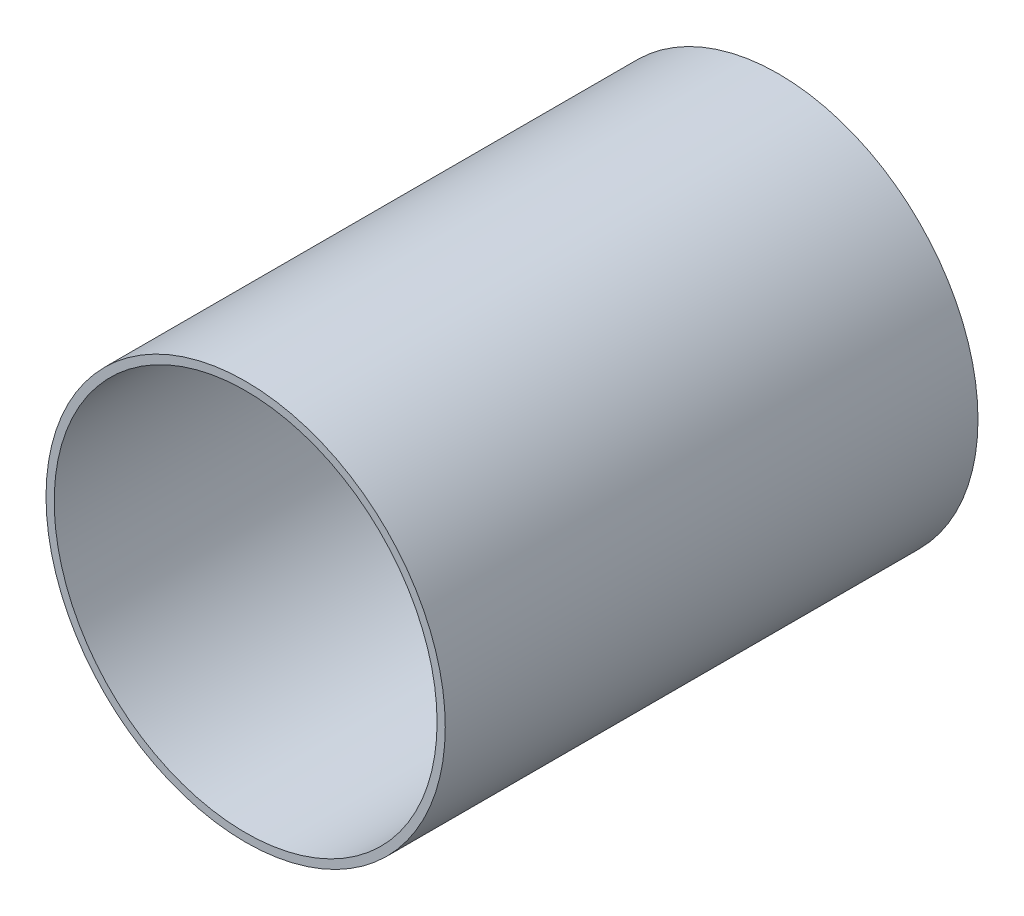
SolidWorks part; units mm, degrees
ref_plane "Front Plane" through (0, 0, 0) normal (0, 0, 1) x (1, 0, 0)
ref_plane "Top Plane" through (0, 0, 0) normal (0, 1, 0) x (1, 0, 0)
ref_plane "Right Plane" through (0, 0, 0) normal (1, 0, 0) x (0, 0, -1)
sketch "Sketch1" plane through (0, 0, 0) normal (0, 0, 1) x (1, 0, 0)
  circle A0 centre (0, 0) radius 38.0746
  circle A1 centre (0, 0) radius 36.5125
  dimension "D1" = 73.025
  dimension "D2" = 76.1492
extrude "Boss-Extrude1" add sketch "Sketch1" along normal mid plane 101.6
equation "\"AIRFRAME_OD\"= 3.091in"
equation "\"AIRFRAME_ID\"= 3.00in"
equation "\"FLAT_T\"= 0.125in"
equation "\"NOSE_EXP_L\"= 3.5in"
equation "\"NOSE_SHOULDER_L\"= 5in"
equation "\"MAIN_L\"= 30in"
equation "\"RECO_COUP_L\"= 6in"
equation "\"RECO_SWITCH_L\"= 1.5in"
equation "\"DROGUE_L\"= 14in"
equation "\"ATS_FORE_COUP_L\"= 4in"
equation "\"ATS_AFT_COUP_L\"= 4in"
equation "\"LOWER_L\"= 16in"
equation "\"FIN_N\"= 4"
equation "\"CR_AFT_X\"= 0.5in"
equation "\"CR_FORE_X\"= 6in"
equation "\"D1@Sketch1\"=\"COUPLER_ID\""
equation "\"D2@Sketch1\"=\"COUPLER_OD\""
equation "\"D1@Boss-Extrude1\"=\"ATS_FORE_COUP_L\""
equation "\"FIN_ROOT\"= 5in"
equation "\"FIN_X\"= 0.75in"
equation "\"MOTOR_OD\"= 2.25in"
equation "\"MOTOR_ID\"= 2.126in"
equation "\"COUPLER_OD\"= 2.998in"
equation "\"COUPLER_ID\"= 2.875in"
